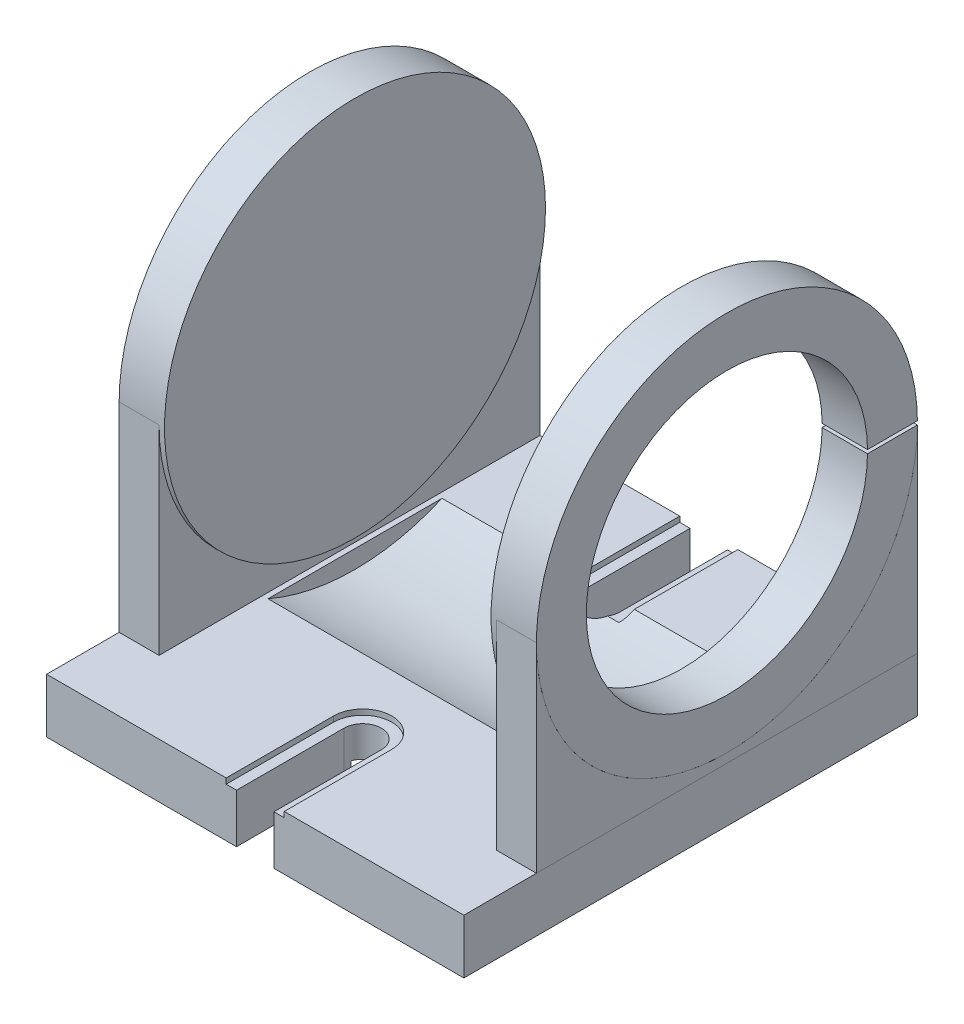
SolidWorks part; units mm, degrees
note: The reader was unsure of these and kept them because the rebuilt part matched: shared geometry of "草图4<3>", "草图6<5>", "草图6<8>", "草图6<10>".
ref_plane "前视基准面" through (0, 0, 0) normal (0, 0, 1) x (1, 0, 0)
ref_plane "上视基准面" through (0, 0, 0) normal (0, 1, 0) x (1, 0, 0)
ref_plane "右视基准面" through (0, 0, 0) normal (1, 0, 0) x (0, 0, -1)
sketch "草图3" plane through (0, 0, 0) normal (0, 1, 0) x (1, 0, 0)
  line L1 (115, -125) -> (-115, -125)
  line L2 (115, -125) -> (115, 125)
  line L3 (115, 125) -> (-115, 125)
  line L4 (-115, -125) -> (-115, 125)
  line L5 (115, -125) -> (-115, 125) construction
  line L6 (115, 125) -> (-115, -125) construction
  point P0 (0, 0)
  dimension "D1" = 250
  dimension "D2" = 230
extrude "凸台-拉伸1" add sketch "草图3" along normal blind 30
sketch "草图4" plane through (0, 30, 0) normal (0, 1, 0) x (1, 0, 0)
  line L0 (-16, -65.753) -> (-16, -125)
  line L1 (-115, -125) -> (115, -125) construction
  line L2 (16, -65.753) -> (16, -125)
  line L3 (-10.305, -65.753) -> (-10.305, -125)
  line L4 (10.305, -65.753) -> (10.305, -125)
  line L5 (-16, -125) -> (16, -125)
  arc A0 (16, -65.753) -> (-16, -65.753) centre (0, -65.753) ccw
  arc A1 (10.305, -65.753) -> (-10.305, -65.753) centre (0, -65.753) ccw
  line M6 (-115, -125) -> (115, -125)
  dimension "D1" = 32
  dimension "D2" = 20.61
extrude "切除-拉伸1" cut sketch "草图4" against normal blind 30 contours L4 A1 L3 M6
extrude "切除-拉伸2" cut sketch "草图4<3>" against normal blind 3 contours A1 L4 L2 A0 L0 L3 M6
sketch "草图4<3>" plane through (0, 30, 0) normal (0, 1, 0) x (1, 0, 0) same geometry as "草图4"
mirror "镜向1" about plane through (0, 0, 0) normal (0, 0, 1) of "切除-拉伸1", "切除-拉伸2"
sketch "草图5" plane through (0, 30, 0) normal (0, 1, 0) x (1, 0, 0)
  line L1 (10.305, -65.753) -> (-10.305, -65.753)
  line L2 (10.305, -65.753) -> (10.305, 65.753)
  line L3 (10.305, 65.753) -> (-10.305, 65.753)
  line L4 (-10.305, -65.753) -> (-10.305, 65.753)
  line L5 (10.305, -65.753) -> (-10.305, 65.753) construction
  line L6 (10.305, 65.753) -> (-10.305, -65.753) construction
  arc A0 (-10.305, 65.753) -> (10.305, 65.753) centre (0, 65.753) ccw construction
  point P0 (0, 0)
extrude "切除-拉伸3" cut sketch "草图5" along normal blind 4 from surface at -30 starting at face at (0, 0, 0)
sketch "草图6" plane through (0, 0, 0) normal (1, 0, 0) x (0, 0, -1)
  line L0 (125, 30) -> (125, 140)
  line L1 (-125, 0) -> (125, 0) construction
  line L2 (-85, 140) -> (-85, 30)
  line L3 (-125, 30) -> (125, 30) construction
  line L4 (-85, 30) -> (125, 30)
  circle A0 centre (20, 140) radius 105
  dimension "D1" = 140
  dimension "D2" = 210
extrude "凸台-拉伸2" add sketch "草图6" against normal blind 25 from surface at 115 contours A0 L4 starting at face at (115, 15, 0)
extrude "凸台-拉伸3" add sketch "草图6<5>" along normal blind 25 from surface at -115 contours A0 starting at face at (-115, 15, 0)
sketch "草图6<5>" plane through (0, 0, 0) normal (1, 0, 0) x (0, 0, -1) same geometry as "草图6"
extrude "凸台-拉伸4" add sketch "草图6<8>" against normal blind 22 from surface at 115 separate body contours A0 L2 L4 L0 starting at face at (115, 140, 85)
sketch "草图6<8>" plane through (0, 0, 0) normal (1, 0, 0) x (0, 0, -1) same geometry as "草图6"
extrude "凸台-拉伸5" add sketch "草图6<10>" along normal blind 22 from surface at -115 contours A0 L2 L4 L0 starting at face at (-115, 140, -125)
sketch "草图6<10>" plane through (0, 0, 0) normal (1, 0, 0) x (0, 0, -1) same geometry as "草图6"
sketch "草图10" plane through (0, 0, 0) normal (1, 0, 0) x (0, 0, -1)
  circle A0 centre (20, 140) radius 120
  dimension "D1" = 240
extrude "切除-拉伸10" cut sketch "草图10" against normal mid plane 180
sketch "草图11" plane through (115, 0, 0) normal (1, 0, 0) x (0, 0, -1)
  circle A0 centre (20, 140) radius 77.5
  dimension "D1" = 155
extrude "切除-拉伸11" cut sketch "草图11" against normal up to next (25 mm away)
ref_plane "基准面1" through (0, 140, 0) normal (0, -1, 0) x (-1, 0, 0)
sketch "草图12" plane through (0, 140, 0) normal (0, -1, 0) x (-1, 0, 0)
  line L1 (-130.6506, -2.8793) -> (-73.0644, -2.8793)
  line L2 (-130.6506, -2.8793) -> (-130.6506, 165.2722)
  line L3 (-130.6506, 165.2722) -> (-73.0644, 165.2722)
  line L4 (-73.0644, -2.8793) -> (-73.0644, 165.2722)
  line L5 (-130.6506, -2.8793) -> (-73.0644, 165.2722) construction
  line L6 (-130.6506, 165.2722) -> (-73.0644, -2.8793) construction
  point P0 (-101.8575, 81.1965)
extrude "切除-拉伸12" cut sketch "草图12" against normal mid plane 2
sketch "草图13" plane through (0, 0, 0) normal (0, 1, 0) x (1, 0, 0)
  line L0 (-112.5, 113) -> (-112.5, 138.3394)
  line L1 (-112.5, 138.3394) -> (-95.5, 138.3394)
  line L2 (-95.5, 138.3394) -> (-95.5, 113)
  line L3 (-93, 125) -> (-115, 125) construction
  circle A0 centre (-104, 113) radius 8.5
  dimension "D1" = 17
  dimension "D2" = 12
extrude "切除-拉伸13" cut sketch "草图13" along normal through all from offset 156 contours A0 L2 L1 L0 | A0
sketch "草图14" plane through (0, 156, 0) normal (0, 1, 0) x (1, 0, 0)
  circle A0 centre (-104, 113) radius 5.5
  dimension "D1" = 11
extrude "切除-拉伸14" cut sketch "草图14" against normal blind 18
sketch "草图15" plane through (0, 0, 0) normal (0, 1, 0) x (1, 0, 0)
  line L0 (115, 124.9952) -> (90, 124.9952) construction
  line L1 (94, 112.9952) -> (94, 134.9565)
  line L2 (94, 134.9565) -> (111, 134.9565)
  line L3 (111, 134.9565) -> (111, 112.9952)
  circle A0 centre (102.5, 112.9952) radius 8.5
  dimension "D1" = 17
  dimension "D2" = 12
extrude "切除-拉伸15" cut sketch "草图15" along normal through all from offset 154 contours A0 | A0 L3 L2 L1
sketch "草图16" plane through (0, 154, 0) normal (0, 1, 0) x (1, 0, 0)
  circle A0 centre (102.5, 112.9952) radius 5.5
  dimension "D1" = 11
extrude "切除-拉伸16" cut sketch "草图16" against normal up to next (13 mm away)
hole_wizard "M10 螺纹孔1" positions "草图17" profile "草图18" tap size "M10" standard "GB"
sketch "草图17" plane through (0, 138, 0) normal (0, 1, 0) x (1, 0, 0)
  point P0 (-104, 113)
  point P3 (102.5, 112.9952)
sketch "草图18" plane through (-104, 138, -113) normal (1, 0, 0) x (0, 0, 1)
  line L0 (0, 0) -> (0, 32.5537)
  line L1 (0, 32.5537) -> (4.25, 30)
  line L2 (4.25, 30) -> (4.25, 0)
  line L5 (4.25, 0) -> (0, 0)
  line L10 (0, 32.5537) -> (-4.25, 30) construction
  line L11 (0, -6.35) -> (0, 107.95) construction
  dimension "螺纹孔钻头直径" = 8.5
  dimension "螺纹孔钻头深度" = 30
  dimension "导头角度" = 118
cosmetic thread "孔螺蚊线1" parameters "D1"=25, "D2"=10
hole_wizard "M10 螺纹孔2" positions "草图19" profile "草图20" tap size "M10" standard "GB"
sketch "草图19" plane through (0, 139, 0) normal (0, 1, 0) x (1, 0, 0)
  point P0 (102.5, 112.9952)
sketch "草图20" plane through (102.5, 139, -112.9952) normal (1, 0, 0) x (0, 0, 1)
  line L0 (0, 0) -> (0, 32.5537)
  line L1 (0, 32.5537) -> (4.25, 30)
  line L2 (4.25, 30) -> (4.25, 0)
  line L5 (4.25, 0) -> (0, 0)
  line L10 (0, 32.5537) -> (-4.25, 30) construction
  line L11 (0, -6.35) -> (0, 107.95) construction
  dimension "螺纹孔钻头直径" = 8.5
  dimension "螺纹孔钻头深度" = 30
  dimension "导头角度" = 118
cosmetic thread "孔螺蚊线2" parameters "D1"=25, "D2"=10
sketch "草图21" plane through (0, 0, 0) normal (0, -1, 0) x (1, 0, 0)
  line L0 (90, 27.9583) -> (90, -67.9583) construction
  line L1 (90, -62.5) -> (-90, -62.5)
  line L2 (90, -62.5) -> (90, 62.5)
  line L3 (90, 62.5) -> (-90, 62.5)
  line L4 (-90, -62.5) -> (-90, 62.5)
  line L5 (90, -62.5) -> (-90, 62.5) construction
  line L6 (90, 62.5) -> (-90, -62.5) construction
  point P0 (0, 0)
  dimension "D1" = 125
extrude "切除-拉伸17" cut sketch "草图21" against normal blind 10
fillet "圆角1" radius 10 4 edges at (90, 5, -62.5) (90, 5, 62.5) (-90, 5, -62.5) (-90, 5, 62.5)
